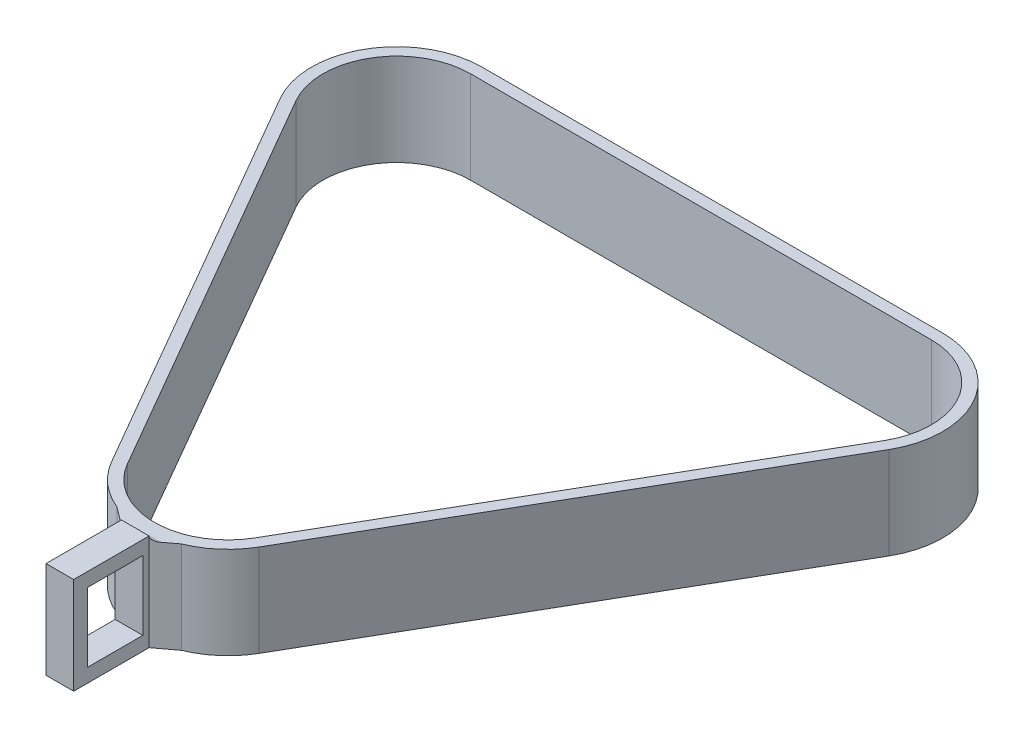
SolidWorks part; units mm, degrees
ref_plane "Front Plane" through (0, 0, 0) normal (0, 0, 1) x (1, 0, 0)
ref_plane "Top Plane" through (0, 0, 0) normal (0, 1, 0) x (1, 0, 0)
ref_plane "Right Plane" through (0, 0, 0) normal (1, 0, 0) x (0, 0, -1)
sketch "Sketch1" plane through (0, 0, 0) normal (0, 1, 0) x (1, 0, 0)
  line L0 (0, 0) -> (100, 0)
  line L1 (100, 0) -> (50, -86.6025)
  line L2 (50, -86.6025) -> (0, 0)
  line L3 (-13.8564, -8) -> (36.1436, -94.6025)
  line L4 (113.8564, -8) -> (63.8564, -94.6025)
  line L5 (100, 16) -> (0, 16)
  line L6 (100, 18.5) -> (0, 18.5)
  line L7 (-16.0215, -9.25) -> (33.9785, -95.8525)
  line L8 (66.0215, -95.8525) -> (116.0215, -9.25)
  circle A0 centre (100, 0) radius 16
  circle A1 centre (50, -86.6025) radius 16
  circle A2 centre (0, 0) radius 16
  circle A5 centre (100, 0) radius 18.5
  circle A6 centre (0, 0) radius 18.5
  circle A7 centre (50, -86.6025) radius 18.5
  dimension "D2" = 32
  dimension "D3" = 37
  dimension "D1" = 100
extrude "Boss-Extrude1" add sketch "Sketch1" along normal blind 20 contours A7 L3 A6 L7 | A7 L4 A1 L3 | A7 L8 A5 L4 | L4 A5 L5 A0 | A6 L5 A5 L6 | L5 A6 L3 A2 region at (-14.2403, 0, -8.2217) region at (50, 0, -17.285) region at (10.0307, 0, 51.9438) region at (95.3064, 0, -17.436) region at (33.4634, 0, 90.788) region at (89.9693, 0, 51.9438)
ref_plane "Plane1" through (50, 0, 0) normal (-1, 0, 0) x (0, 0, 1)
sketch "Sketch2" plane through (50, 0, 0) normal (-1, 0, 0) x (0, 0, 1)
  line L1 (105.1025, 0) -> (123.1025, 0)
  line L2 (105.1025, 0) -> (105.1025, 21)
  line L3 (105.1025, 21) -> (123.1025, 21)
  line L4 (123.1025, 0) -> (123.1025, 21)
  line L5 (108.1025, 3) -> (120.1025, 3)
  line L6 (108.1025, 3) -> (108.1025, 18)
  line L7 (108.1025, 18) -> (120.1025, 18)
  line L8 (120.1025, 3) -> (120.1025, 18)
  dimension "D1" = 18
  dimension "D2" = 21
  dimension "D3" = 12
  dimension "D4" = 15
  dimension "D5" = 3
  dimension "D6" = 3
extrude "Boss-Extrude2" add sketch "Sketch2" along normal blind 3 and the other way blind 3 separate body
sketch "Sketch3" plane through (0, 21, 0) normal (0, 1, 0) x (1, 0, 0)
  line L0 (47, -106.7271) -> (43, -103.7271)
  line L1 (43, -103.7271) -> (57, -103.7271)
  line L2 (57, -103.7271) -> (53, -106.7271)
  line L3 (47, -123.1025) -> (47, -105.1025) construction
  line L4 (53, -123.1025) -> (53, -105.1025) construction
  line L7 (53, -105.1025) -> (47, -105.1025)
  line L8 (47, -105.1025) -> (47, -123.1025)
  line L9 (47, -123.1025) -> (53, -123.1025)
  line L10 (53, -123.1025) -> (53, -105.1025)
  line L12 (47, -106.7271) -> (47, -123.1025)
  line L13 (47, -123.1025) -> (53, -123.1025)
  line L14 (53, -123.1025) -> (53, -106.7271)
  arc A0 (33.9785, -95.8525) -> (66.0215, -95.8525) centre (50, -86.6025) ccw construction
  point P2 (47, -106.6723)
  point P11 (0, 0)
  point P13 (0, 0)
  point P17 (53, -107.1246)
  point P20 (0, 0)
  line M2 (53, -105.1025) -> (47, -105.1025)
  dimension "D1" = 5
  dimension "D3" = 14
  dimension "D2" = 0
extrude "Boss-Extrude3" add sketch "Sketch3" against normal blind 21 contours L2 L1 L0 M2 region at (50, 21, 104.5998)
sketch "Sketch4" plane through (50, 0, 0) normal (-1, 0, 0) x (0, 0, 1)
  line L1 (103.7271, 20) -> (106.7271, 20)
  line L2 (103.7271, 20) -> (103.7271, 21)
  line L3 (103.7271, 21) -> (106.7271, 21)
  line L4 (106.7271, 20) -> (106.7271, 21)
extrude "Cut-Extrude1" cut sketch "Sketch4" against normal blind 30 and the other way blind 30
fillet "Fillet1" radius 1 1 edges at (50, 20, 106.7271)
